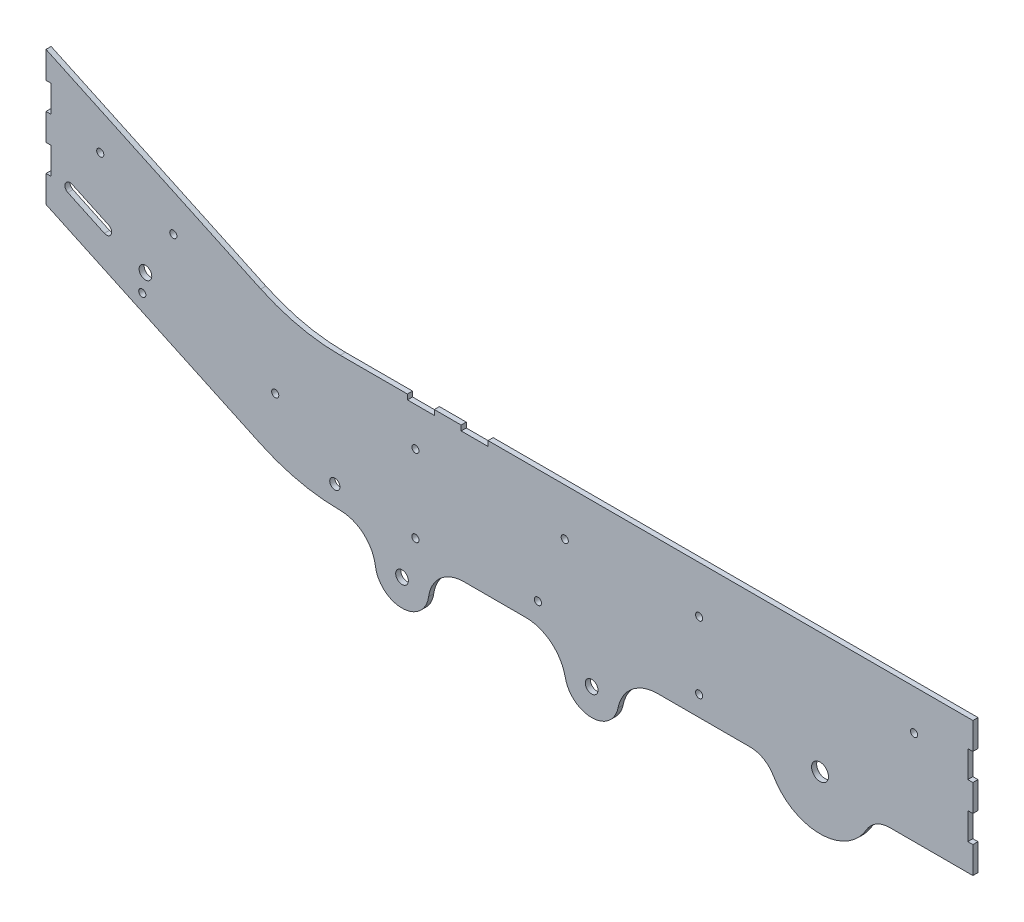
SolidWorks part; units mm, degrees
material "1060 Alloy"
ref_plane "Front Plane" through (0, 0, 0) normal (0, 0, 1) x (1, 0, 0)
ref_plane "Top Plane" through (0, 0, 0) normal (0, 1, 0) x (1, 0, 0)
ref_plane "Right Plane" through (0, 0, 0) normal (1, 0, 0) x (0, 0, -1)
sketch "standoff holes lower" plane through (0, 0, 0) normal (0, 0, 1) x (1, 0, 0)
  circle A7 centre (95.25, 85.725) radius 3.3782
  circle A8 centre (95.25, 12.7) radius 3.3782
  circle A9 centre (171.45, 12.7) radius 3.3782
  circle A10 centre (171.45, 85.725) radius 3.3782
  circle A12 centre (298.45, 12.7) radius 3.3782
  circle A13 centre (450.85, 85.725) radius 3.3782
  circle A16 centre (273.05, 85.725) radius 3.3782
  point P21 (0, 0)
sketch "axle holes lower" plane through (0, 0, 0) normal (0, 0, 1) x (1, 0, 0)
  line L10 (514.35, 98.425) -> (75.4368, 98.425) construction
  line L11 (66.0749, 94.3067) -> (3.3381, 25.8666) construction
  line L12 (0, 17.2849) -> (0, 12.7) construction
  line L13 (12.7, 0) -> (514.35, 0) construction
  line L14 (527.05, 12.7) -> (527.05, 85.725) construction
  circle A1 centre (247.65, 15.24) radius 4.826
  circle A4 centre (19.05, 19.05) radius 4.826
  arc A10 (527.05, 85.725) -> (514.35, 98.425) centre (514.35, 85.725) ccw construction
  arc A11 (75.4368, 98.425) -> (66.0749, 94.3067) centre (75.4368, 85.725) ccw construction
  arc A12 (3.3381, 25.8666) -> (0, 17.2849) centre (12.7, 17.2849) ccw construction
  arc A13 (0, 12.7) -> (12.7, 0) centre (12.7, 12.7) ccw construction
  arc A14 (514.35, 0) -> (527.05, 12.7) centre (514.35, 12.7) ccw construction
  circle A15 centre (476.25, 19.05) radius 4.826
sketch "lower box" plane through (0, 0, 0) normal (0, 0, 1) x (1, 0, 0)
  line L1 (622.3, 0) -> (-254, 0) construction
  line L2 (622.3, 0) -> (622.3, 25.4) construction
  line L3 (622.3, 127) -> (-254, 127) construction
  line L4 (-254, 0) -> (-254, 127) construction
  line L6 (527.05, 12.7) -> (527.05, 85.725) construction
  line L7 (622.3, 101.6) -> (622.3, 127) construction
  line L8 (622.3, 101.6) -> (617.474, 101.6) construction
  line L10 (622.3, 76.2) -> (617.474, 76.2) construction
  line L11 (617.474, 101.6) -> (617.474, 76.2) construction
  line L12 (622.3, 50.8) -> (617.474, 50.8) construction
  line L14 (622.3, 25.4) -> (617.474, 25.4) construction
  line L15 (617.474, 50.8) -> (617.474, 25.4) construction
  line L16 (622.3, 50.8) -> (622.3, 76.2) construction
  dimension "D1" = 127
  dimension "D2" = 876.3
  dimension "D3" = 95.25
  dimension "D4" = 4.826
sketch "alxe holes upper" plane through (0, 0, 0) normal (0, 0, 1) x (1, 0, 0)
  line L0 (-219.7848, 130.4205) -> (-230.5193, 107.4003) construction
  line L1 (-230.5193, 107.4003) -> (8.3155, -3.9702) construction
  line L3 (8.3155, -3.9702) -> (19.05, 19.05) construction
  line L4 (622.3, 0) -> (-254, 0) construction
  circle A0 centre (19.05, 19.05) radius 4.826 construction
  circle A2 centre (-219.7848, 130.4205) radius 4.826
  circle A3 centre (19.05, 19.05) radius 4.826
  dimension "D4" = 25
  dimension "D1" = 25.4
  dimension "D2" = 25.4
  dimension "D3" = 263.525
sketch "standoff holes upper" plane through (0, 0, 0) normal (0, 0, 1) x (1, 0, 0)
  line L0 (-162.9561, 84.3028) -> (-166.1764, 77.3967) construction
  line L1 (-226.6865, 105.613) -> (11.2395, -5.3337) construction
  line L4 (-37.2808, 64.9356) -> (-55.5295, 25.8012) construction
  line L5 (-230.5193, 107.4003) -> (8.3155, -3.9702) construction
  circle A2 centre (-162.9561, 84.3028) radius 3.3782
  circle A3 centre (-37.2808, 64.9356) radius 3.3782
  dimension "D2" = 7.62
  dimension "D1" = 43.18
sketch "upper shadow" plane through (0, 0, 0) normal (0, 0, 1) x (1, 0, 0)
  line L0 (-230.5193, 107.4003) -> (8.3155, -3.9702) construction
  line L4 (33.2535, 40.1076) -> (-204.2179, 150.8423) construction
  line L5 (-230.5193, 107.4003) -> (8.3155, -3.9702) construction
  arc A4 (8.3155, -3.9702) -> (33.2535, 40.1076) centre (19.05, 19.05) ccw construction
  arc A5 (-204.2179, 150.8423) -> (-230.5193, 107.4003) centre (-216.8161, 128.7868) ccw construction
  dimension "D1" = 25.4
  dimension "D2" = 25.4
sketch "upper box" plane through (0, 0, 0) normal (0, 0, 1) x (1, 0, 0)
  line L0 (-15.224, 0) -> (-254, 111.3431) construction
  line L1 (622.3, 0) -> (-254, 0) construction
  line L2 (-254, 111.3431) -> (-254, 136.7431) construction
  line L3 (-254, 238.3431) -> (257.1283, 0) construction
  line L4 (12.7, 0) -> (514.35, 0) construction
  line L5 (-254, 0) -> (-254, 127) construction
  line L6 (-230.5193, 107.4003) -> (8.3155, -3.9702) construction
  line L7 (-254, 212.9431) -> (-254, 238.3431) construction
  line L8 (-254, 212.9431) -> (-249.174, 212.9431) construction
  line L9 (-254, 162.1431) -> (-254, 187.5431) construction
  line L10 (-254, 187.5431) -> (-249.174, 187.5431) construction
  line L11 (-249.174, 212.9431) -> (-249.174, 187.5431) construction
  line L12 (-254, 162.1431) -> (-249.174, 162.1431) construction
  line L14 (-254, 136.7431) -> (-249.174, 136.7431) construction
  line L15 (-249.174, 162.1431) -> (-249.174, 136.7431) construction
  dimension "D1" = 127
  dimension "D2" = 6.35
  dimension "D3" = 4.826
sketch "outer face" plane through (0, 0, 0) normal (0, 0, 1) x (1, 0, 0)
  line L0 (622.3, 0) -> (-254, 0) construction
  line L1 (622.3, 0) -> (622.3, 25.4) construction
  line L2 (622.3, 25.4) -> (617.474, 25.4) construction
  line L3 (617.474, 50.8) -> (617.474, 25.4) construction
  line L4 (622.3, 50.8) -> (617.474, 50.8) construction
  line L5 (622.3, 50.8) -> (622.3, 76.2) construction
  line L6 (622.3, 76.2) -> (617.474, 76.2) construction
  line L7 (617.474, 101.6) -> (617.474, 76.2) construction
  line L8 (622.3, 101.6) -> (622.3, 127) construction
  line L9 (622.3, 101.6) -> (617.474, 101.6) construction
  line L10 (622.3, 127) -> (-254, 127) construction
  line L11 (-254, 238.3431) -> (257.1283, 0) construction
  line L12 (-254, 212.9431) -> (-254, 238.3431) construction
  line L13 (-254, 212.9431) -> (-249.174, 212.9431) construction
  line L14 (-249.174, 212.9431) -> (-249.174, 187.5431) construction
  line L15 (-249.174, 162.1431) -> (-249.174, 136.7431) construction
  line L16 (-254, 136.7431) -> (-249.174, 136.7431) construction
  line L17 (-254, 111.3431) -> (-254, 136.7431) construction
  line L18 (-15.224, 0) -> (-254, 111.3431) construction
  line L19 (-254, 162.1431) -> (-249.174, 162.1431) construction
  line L20 (-254, 162.1431) -> (-254, 187.5431) construction
  line L21 (-254, 187.5431) -> (-249.174, 187.5431) construction
  line L22 (622.3, 0) -> (24.1933, 0)
  line L23 (622.3, 0) -> (622.3, 25.4)
  line L24 (622.3, 25.4) -> (617.474, 25.4)
  line L25 (617.474, 50.8) -> (617.474, 25.4)
  line L26 (622.3, 50.8) -> (617.474, 50.8)
  line L27 (622.3, 50.8) -> (622.3, 76.2)
  line L28 (622.3, 76.2) -> (617.474, 76.2)
  line L29 (617.474, 101.6) -> (617.474, 76.2)
  line L30 (622.3, 101.6) -> (622.3, 127)
  line L31 (622.3, 101.6) -> (617.474, 101.6)
  line L32 (622.3, 127) -> (24.1933, 127)
  line L33 (-254, 238.3431) -> (-50.9483, 143.6585)
  line L34 (-254, 212.9431) -> (-254, 238.3431)
  line L35 (-254, 212.9431) -> (-249.174, 212.9431)
  line L36 (-249.174, 212.9431) -> (-249.174, 187.5431)
  line L37 (-249.174, 162.1431) -> (-249.174, 136.7431)
  line L38 (-254, 136.7431) -> (-249.174, 136.7431)
  line L39 (-254, 111.3431) -> (-254, 136.7431)
  line L40 (-50.9483, 16.6585) -> (-254, 111.3431)
  line L41 (-254, 162.1431) -> (-249.174, 162.1431)
  line L42 (-254, 162.1431) -> (-254, 187.5431)
  line L43 (-254, 187.5431) -> (-249.174, 187.5431)
  arc A0 (-50.9483, 16.6585) -> (24.1933, 0) centre (24.1933, 177.8) ccw
  arc A1 (24.1933, 127) -> (-50.9483, 143.6585) centre (24.1933, 304.8) cw
  dimension "D1" = 177.8
extrude "Boss-Extrude1" add sketch "outer face" along normal blind 4.826
sketch "Sketch5" plane through (0, 0, 4.826) normal (0, 0, 1) x (1, 0, 0)
  line L0 (-254, 238.3431) -> (257.1283, 0) construction
  line L1 (-162.9561, 84.3028) -> (-120.2162, 175.9587) construction
  line L2 (622.3, 127) -> (24.1933, 127) construction
  line L3 (-202.695, 179.3869) -> (-133.6344, 147.1834) construction
  line L4 (617.474, 76.2) -> (617.474, 101.6) construction
  line L5 (622.3, 127) -> (24.1933, 127) construction
  line L6 (414.2486, -29.6609) -> (414.2486, 95.7516) construction
  line L7 (24.1933, 0) -> (622.3, 0) construction
  circle A0 centre (-162.9561, 84.3028) radius 3.3782 construction
  circle A1 centre (-37.2808, 64.9356) radius 3.3782 construction
  circle A9 centre (-162.9561, 84.3028) radius 3.3782
  circle A10 centre (-37.2808, 64.9356) radius 3.3782
  circle A11 centre (95.25, 85.725) radius 3.3782
  circle A12 centre (95.25, 12.7) radius 3.3782
  circle A13 centre (211.0486, 19.05) radius 3.3782
  circle A14 centre (236.4486, 82.55) radius 3.3782
  circle A15 centre (363.4486, 82.55) radius 3.3782
  circle A16 centre (363.4486, 19.05) radius 3.3782
  circle A17 centre (566.674, 88.9) radius 3.3782
  circle A18 centre (-133.6344, 147.1834) radius 3.3782
  circle A19 centre (-202.695, 179.3869) radius 3.3782
  dimension "D9" = 127
  dimension "D10" = 152.4
  dimension "D11" = 19.05
  dimension "D12" = 44.45
  dimension "D13" = 6.7564
  dimension "D7" = 19.05
  dimension "D1" = 31.75
  dimension "D2" = 76.2
  dimension "D3" = 38.1
  dimension "D4" = 50.8
  dimension "D5" = 44.45
  dimension "D6" = 50.8
  dimension "D8" = 50.8
extrude "standoff hole" cut sketch "Sketch5" against normal through all
sketch "Sketch6" plane through (0, 0, 4.826) normal (0, 0, 1) x (1, 0, 0)
  circle A0 centre (-219.7848, 130.4205) radius 4.826 construction
  circle A1 centre (19.05, 19.05) radius 4.826 construction
  circle A2 centre (247.65, 15.24) radius 4.826 construction
  circle A4 centre (-219.7848, 130.4205) radius 4.826
  circle A5 centre (19.05, 19.05) radius 4.826
  circle A6 centre (247.65, 15.24) radius 4.826 construction
extrude "axle holes" cut sketch "Sketch6" against normal through all
sketch "Sketch7" plane through (0, 0, 4.826) normal (0, 0, 1) x (1, 0, 0)
  line L0 (-231.2949, 135.7877) -> (-196.7645, 119.686) construction
  line L1 (-229.2553, 140.1616) -> (-194.725, 124.0598)
  line L2 (-233.3344, 131.4139) -> (-198.8041, 115.3121)
  line L3 (-230.5193, 107.4003) -> (8.3155, -3.9702) construction
  circle A0 centre (-219.7848, 130.4205) radius 4.826 construction
  circle A1 centre (-219.7848, 130.4205) radius 4.826
  arc A2 (-229.2553, 140.1616) -> (-233.3344, 131.4139) centre (-231.2949, 135.7877) ccw
  arc A3 (-198.8041, 115.3121) -> (-194.725, 124.0598) centre (-196.7645, 119.686) ccw
  point P5 (-214.0297, 127.7369)
  circle M6 centre (-219.7848, 130.4205) radius 4.826
  dimension "D1" = 38.1
  dimension "D2" = 12.7
extrude "front slot" cut sketch "Sketch7" against normal through all contours L1 A2 L2 A1 M6 | L2 A3 L1 region at (-228.975, 134.706, 4.826) region at (-204.8394, 123.4514, 4.826)
sketch "Sketch8" plane through (0, 0, 4.826) normal (0, 0, 1) x (1, 0, 0)
  line L0 (113.0933, 127) -> (113.0933, 122.174) construction
  line L1 (87.6933, 122.174) -> (113.0933, 122.174)
  line L2 (87.6933, 122.174) -> (87.6933, 127)
  line L3 (87.6933, 127) -> (113.0933, 127)
  line L4 (113.0933, 122.174) -> (113.0933, 127)
  line L5 (622.3, 127) -> (24.1933, 127) construction
  line L6 (113.0933, 122.174) -> (138.4933, 122.174) construction
  line L7 (138.4933, 122.174) -> (163.8933, 122.174)
  line L8 (138.4933, 122.174) -> (138.4933, 127)
  line L9 (138.4933, 127) -> (163.8933, 127)
  line L10 (163.8933, 122.174) -> (163.8933, 127)
  line L11 (62.2933, 122.174) -> (189.2933, 122.174)
  line L12 (62.2933, 122.174) -> (62.2933, 127)
  line L13 (62.2933, 127) -> (189.2933, 127)
  line L14 (189.2933, 122.174) -> (189.2933, 127)
  line L15 (163.8933, 127) -> (163.8933, 122.174) construction
  point P18 (125.7933, 122.174)
  point P19 (125.7933, 122.174)
  line M29 (622.3, 127) -> (24.1933, 127)
  dimension "D1" = 127
extrude "top slots" cut sketch "Sketch8" against normal through all contours L1 L4 L2 M29 | L7 L10 L8 M29 region at (100.3933, 124.587, 4.826) region at (151.1933, 124.587, 4.826)
sketch "Sketch9" plane through (0, 0, 4.826) normal (0, 0, 1) x (1, 0, 0)
  line L0 (365.4629, -63.5) -> (553.974, -63.5) construction
  line L1 (24.1933, 0) -> (622.3, 0) construction
  line L3 (553.974, -63.5) -> (553.974, 63.787) construction
  line L4 (617.474, 25.4) -> (617.474, 50.8) construction
  line L5 (24.1933, 0) -> (622.3, 0)
  circle A0 centre (477.774, 12.7) radius 76.2 construction
  circle A1 centre (477.774, 12.7) radius 8
  arc A2 (433.7799, -12.7) -> (521.7681, -12.7) centre (477.774, 12.7) ccw
  arc A3 (543.7651, 0) -> (521.7681, -12.7) centre (543.7651, -25.4) ccw
  arc A4 (433.7799, -12.7) -> (411.7829, 0) centre (411.7829, -25.4) ccw
  dimension "D1" = 152.4
  dimension "D4" = 16
  dimension "D5" = 50.8
  dimension "D6" = 25.4
  dimension "D7" = 25.4
  dimension "D2" = 63.5
  dimension "D3" = 63.5
extrude "back axle extension" add sketch "Sketch9" against normal up to surface (4.826 mm away) contours A4 A2 A3 L5 region at (477.774, -15.4671, 4.826) up to face at (-214.0297, 127.7369, 0)
sketch "Sketch11" plane through (0, 0, 4.826) normal (0, 0, 1) x (1, 0, 0)
  line L0 (24.1933, 0) -> (411.7829, 0) construction
  line L1 (24.1933, 0) -> (411.7829, 0)
  line L2 (561.7812, -62.775) -> (321.8375, -62.775) construction
  line L3 (199.6366, 0) -> (324.1114, 0)
  arc A0 (471.7538, 87.9345) -> (489.1691, 87.3098) centre (477.774, 12.7) ccw construction
  arc A1 (471.7538, 87.9345) -> (489.1691, 87.3098) centre (477.774, 12.7) ccw
  circle A2 centre (261.874, -25.5) radius 37.275 construction
  arc A5 (258.0857, 11.582) -> (275.1308, 9.338) centre (261.874, -25.5) ccw construction
  arc A6 (258.0857, 11.582) -> (275.1308, 9.338) centre (261.874, -25.5) ccw construction
  arc A7 (236.9791, -30.54) -> (286.7689, -30.54) centre (261.874, -25.5) ccw
  arc A8 (324.1114, 0) -> (286.7689, -30.54) centre (324.1114, -38.1) ccw
  arc A9 (236.9791, -30.54) -> (199.6366, 0) centre (199.6366, -38.1) ccw
  dimension "D1" = 215.9
  dimension "D2" = 25.4
  dimension "D3" = 38.1
extrude "lower small axle extension" add sketch "Sketch11" against normal up to surface (4.826 mm away) contours A9 A7 A8 L1 region at (261.874, -20.0987, 4.826) up to face at (-214.0297, 127.7369, 0)
sketch "Sketch13" plane through (0, 0, 4.826) normal (0, 0, 1) x (1, 0, 0)
  line L0 (247.3066, -62.775) -> (540.2367, -62.775) construction
  line L1 (-361.4832, 140.4439) -> (-108.3874, 22.4235) construction
  line L2 (-229.2553, 140.1616) -> (-194.725, 124.0598) construction
  line L3 (24.1933, 0) -> (199.6366, 0) construction
  line L4 (24.1933, 0) -> (199.6366, 0)
  arc A0 (471.7538, 87.9345) -> (489.1691, 87.3098) centre (477.774, 12.7) ccw construction
  arc A1 (258.0857, 11.582) -> (275.1308, 9.338) centre (261.874, -25.5) ccw construction
  arc A2 (471.7538, 87.9345) -> (489.1691, 87.3098) centre (477.774, 12.7) ccw construction
  arc A3 (258.0857, 11.582) -> (275.1308, 9.338) centre (261.874, -25.5) ccw construction
  circle A5 centre (82.5849, -25.5) radius 37.275 construction
  arc A6 (-198.8041, 115.3121) -> (-194.725, 124.0598) centre (-196.7645, 119.686) ccw construction
  arc A7 (-198.8041, 115.3121) -> (-194.725, 124.0598) centre (-196.7645, 119.686) ccw construction
  circle A8 centre (-196.7645, 119.686) radius 50.8 construction
  arc A9 (57.4225, -28.9659) -> (107.7473, -28.9659) centre (82.5849, -25.5) ccw
  arc A12 (236.9791, -30.54) -> (286.7689, -30.54) centre (261.874, -25.5) ccw construction
  arc A13 (140.9765, 0) -> (107.7473, -28.9659) centre (140.9765, -33.543) ccw
  arc A14 (57.4225, -28.9659) -> (24.1933, 0) centre (24.1933, -33.543) ccw
  dimension "D1" = 101.6
extrude "front small axle extension" add sketch "Sketch13" against normal up to surface (4.826 mm away) contours A14 A9 A13 L4 region at (82.5849, -20.4486, 4.826) up to face at (-214.0297, 127.7369, 0)
sketch "Sketch14" plane through (0, 0, 4.826) normal (0, 0, 1) x (1, 0, 0)
  line L0 (-254, 111.3431) -> (-50.9483, 16.6585) construction
  line L1 (-254, 111.3431) -> (-50.9483, 16.6585)
  line L2 (-267.5177, 96.6271) -> (94.0166, -71.9591) construction
  line L3 (-227.5206, 77.9761) -> (-175.6892, 189.1288) construction
  arc A0 (78.7966, 11.582) -> (95.8417, 9.338) centre (82.5849, -25.5) ccw construction
  arc A1 (78.7966, 11.582) -> (95.8417, 9.338) centre (82.5849, -25.5) ccw
  circle A2 centre (-160.0111, 102.5476) radius 50.8 construction
  dimension "D1" = 101.6
  dimension "D2" = 38.1
sketch "Sketch10" plane through (0, 0, 4.826) normal (0, 0, 1) x (1, 0, 0)
  circle A0 centre (477.774, 12.7) radius 8
  circle A1 centre (261.874, -25.5) radius 6
  circle A2 centre (82.5849, -25.5) radius 6
  circle A3 centre (-160.0111, 102.5476) radius 6
  dimension "D1" = 16
  dimension "D2" = 12
  dimension "D3" = 12
extrude "new axle holes" cut sketch "Sketch10" against normal through all
equation "\"w\"= .19"
equation "\"D4@lower box\" = \"w\""
equation "\"D3@upper box\"=\"w\""
equation "\"D1@Boss-Extrude1\"=\"w\""
